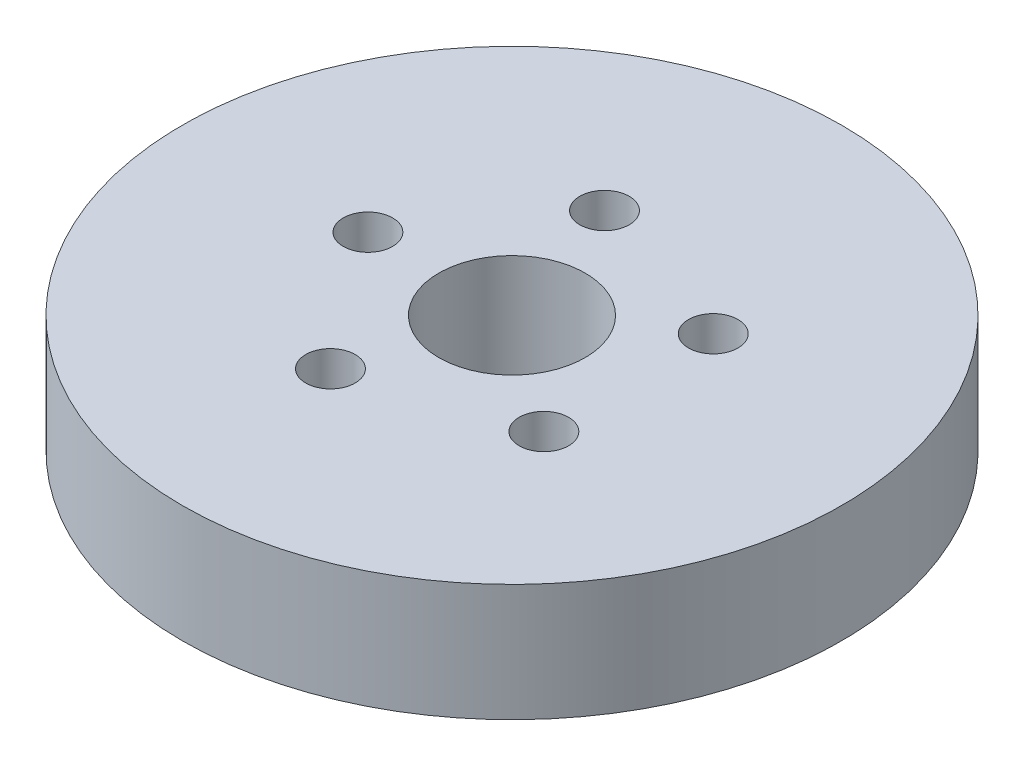
SolidWorks part; units mm, degrees
ref_plane "Front Plane" through (0, 0, 0) normal (0, 0, 1) x (1, 0, 0)
ref_plane "Top Plane" through (0, 0, 0) normal (0, 1, 0) x (1, 0, 0)
ref_plane "Right Plane" through (0, 0, 0) normal (1, 0, 0) x (0, 0, -1)
sketch "Sketch1" plane through (0, 0, 0) normal (0, 1, 0) x (1, 0, 0)
  circle A0 centre (0, 0) radius 67.5
  dimension "FLANGE_OD" = 135
extrude "Boss-Extrude1" add sketch "Sketch1" along normal blind 24
sketch "Sketch2" plane through (0, 0, 0) normal (0, 1, 0) x (1, 0, 0)
  circle A0 centre (0, 0) radius 15
  dimension "BORE_D" = 30
extrude "Cut-Extrude1" cut sketch "Sketch2" along normal through all
sketch "Sketch3" plane through (0, 24, 0) normal (0, 1, 0) x (1, 0, 0)
  circle A0 centre (0, 0) radius 29.5112 construction
  circle A1 centre (-29.5112, 0) radius 5.0653
  dimension "BOLT_D" = 10.1307
  dimension "BOLT_PCD" = 59.0225
extrude "Cut-Extrude2" cut sketch "Sketch3" against normal blind 21.4816
pattern_circular "CirPattern1" count 5 over 360 about axis through (0, 0, 0) along (0, 1, 0) of "Cut-Extrude2"
